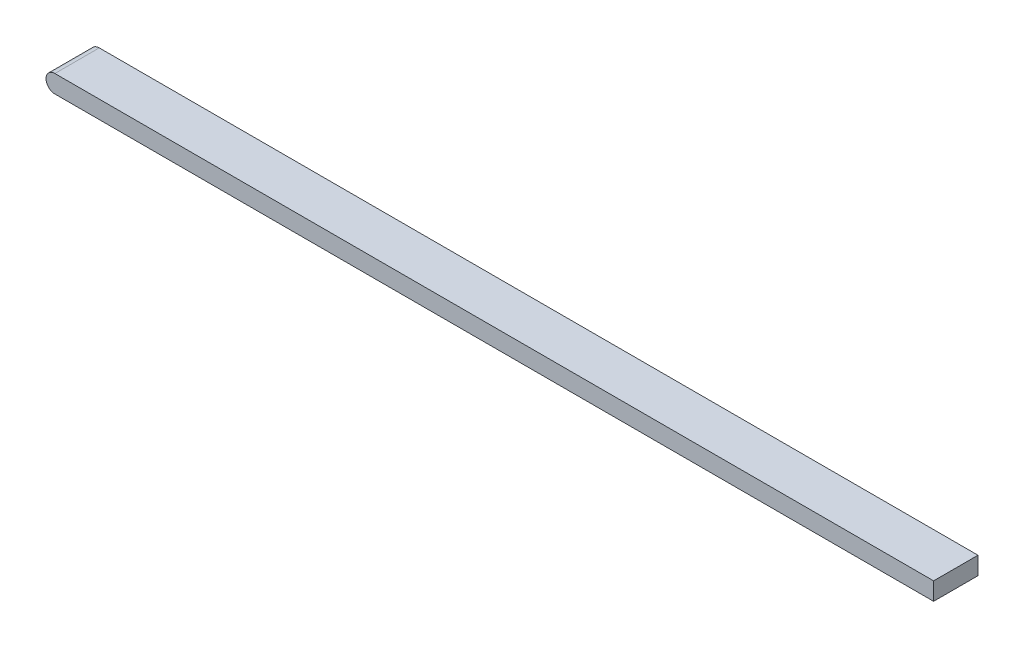
SolidWorks part; units mm, degrees
ref_plane "Front Plane" through (0, 0, 0) normal (0, 0, 1) x (1, 0, 0)
ref_plane "Top Plane" through (0, 0, 0) normal (0, 1, 0) x (1, 0, 0)
ref_plane "Right Plane" through (0, 0, 0) normal (1, 0, 0) x (0, 0, -1)
sketch "Sketch1" plane through (0, 0, 0) normal (0, 1, 0) x (1, 0, 0)
  line L1 (0, 0) -> (1000, 0)
  line L2 (0, 0) -> (0, 50)
  line L3 (0, 50) -> (1000, 50)
  line L4 (1000, 0) -> (1000, 50)
  dimension "D1" = 50
  dimension "D2" = 1000
extrude "Boss-Extrude1" add sketch "Sketch1" along normal blind 20
fillet "Fillet1" radius 10 2 edges at (0, 0, -25) (0, 20, -25)
